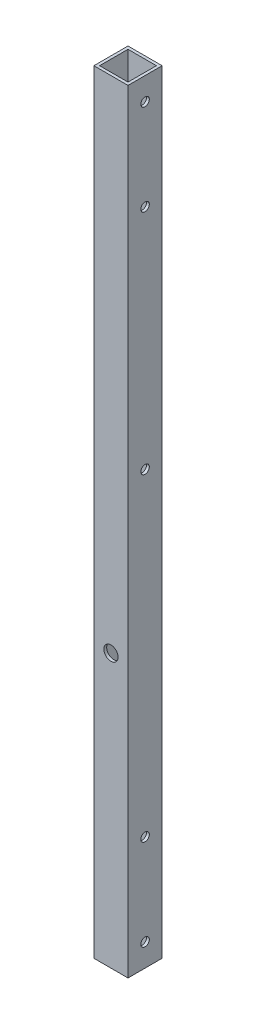
SolidWorks part; units mm, degrees
material "6061 Alloy"
ref_plane "Front Plane" through (0, 0, 0) normal (0, 0, 1) x (1, 0, 0)
ref_plane "Top Plane" through (0, 0, 0) normal (0, 1, 0) x (1, 0, 0)
ref_plane "Right Plane" through (0, 0, 0) normal (1, 0, 0) x (0, 0, -1)
sketch "Sketch1" plane through (0, 0, 0) normal (0, 1, 0) x (1, 0, 0)
  line L1 (-9.525, -9.525) -> (9.525, -9.525)
  line L2 (-9.525, -9.525) -> (-9.525, 9.525)
  line L3 (-9.525, 9.525) -> (9.525, 9.525)
  line L4 (9.525, -9.525) -> (9.525, 9.525)
  line L5 (-9.525, -9.525) -> (9.525, 9.525) construction
  line L6 (-9.525, 9.525) -> (9.525, -9.525) construction
  line L7 (-7.9375, 7.9375) -> (7.9375, 7.9375)
  line L8 (-7.9375, 7.9375) -> (-7.9375, -7.9375)
  line L9 (-7.9375, -7.9375) -> (7.9375, -7.9375)
  line L10 (7.9375, 7.9375) -> (7.9375, -7.9375)
  line L11 (-7.9375, 7.9375) -> (7.9375, -7.9375) construction
  line L12 (-7.9375, -7.9375) -> (7.9375, 7.9375) construction
  point P0 (0, 0)
  point P6 (0, 0)
  dimension "D1" = 19.05
  dimension "D2" = 19.05
  dimension "D3" = 1.5875
  dimension "D4" = 1.5875
extrude "Boss-Extrude1" add sketch "Sketch1" along normal blind 431.8
ref_plane "Plane1" through (0, 215.9, 0) normal (0, -1, 0) x (-1, 0, 0)
ref_axis "Axis1" through (0, 215.9, -10.4775) along (0, 0, 1)
sketch "Sketch2" plane through (0, 0, 9.525) normal (0, 0, 1) x (1, 0, 0)
  line L0 (0, 0) -> (0, 152.4) construction
  line L1 (-9.525, 0) -> (9.525, 0) construction
  circle A2 centre (0, 152.4) radius 3.9687
extrude "Cut-Extrude1" cut sketch "Sketch2" against normal up to next
sketch "Sketch3" plane through (0, 0, 0) normal (1, 0, 0) x (0, 0, -1)
  line L0 (0, 0) -> (0, 12.7) construction
  line L1 (0, 12.7) -> (0, 63.5) construction
  line L2 (0, 63.5) -> (0, 241.3) construction
  line L3 (0, 241.3) -> (0, 368.3) construction
  line L4 (0, 368.3) -> (0, 419.1) construction
  circle A0 centre (0, 12.7) radius 2.3813
  circle A1 centre (0, 63.5) radius 2.3812
  circle A2 centre (0, 241.3) radius 2.3812
  circle A3 centre (0, 368.3) radius 2.3813
  circle A4 centre (0, 419.1) radius 2.3813
extrude "Cut-Extrude2" cut sketch "Sketch3" against normal through all both and the other way through all
